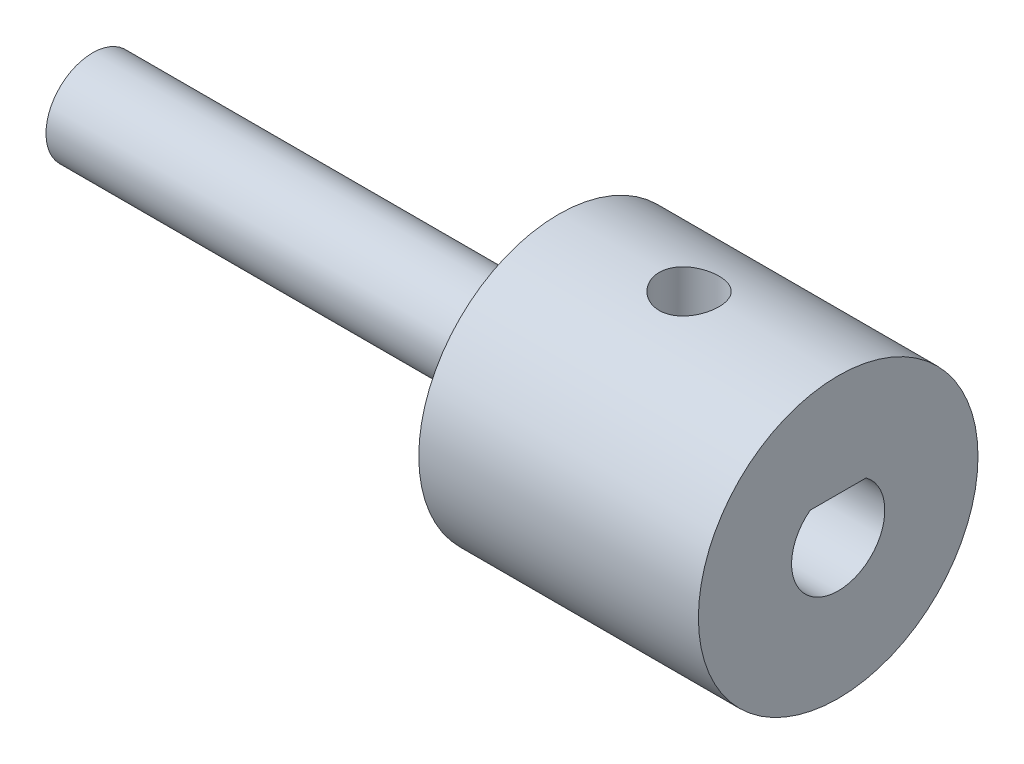
SolidWorks part; units mm, degrees
ref_plane "Front Plane" through (0, 0, 0) normal (0, 0, 1) x (1, 0, 0)
ref_plane "Top Plane" through (0, 0, 0) normal (0, 1, 0) x (1, 0, 0)
ref_plane "Right Plane" through (0, 0, 0) normal (1, 0, 0) x (0, 0, -1)
sketch "Sketch2" plane through (0, 0, 0) normal (0, 0, 1) x (1, 0, 0)
  line L0 (15, 0) -> (15, 7.5)
  line L1 (22, 0) -> (-22, 0) construction
  line L2 (15, 7.5) -> (0, 7.5)
  line L3 (0, 7.5) -> (0, 2.5)
  line L4 (0, 2.5) -> (-25, 2.5)
  line L5 (-25, 2.5) -> (-25, 0)
  line L6 (0, -4.125) -> (0, 4.125) construction
  line L7 (15, 0) -> (-25, 0) construction
  line L8 (15, 0) -> (-25, 0)
  point P10 (0, 5)
  point P11 (-25, 1.25)
  dimension "D1" = 7.5
  dimension "D2" = 2.5
  dimension "D3" = 15
  dimension "D4" = 40
revolve "Revolve1" add sketch "Sketch2" angle 360 about L7
sketch "Sketch3" plane through (15, 0, 0) normal (1, 0, 0) x (0, 0, -1)
  line L0 (-1.5, 2) -> (1.5, 2)
  line L1 (8.25, 0) -> (-8.25, 0) construction
  arc A0 (-1.5, 2) -> (1.5, 2) centre (0, 0) ccw
  dimension "D1" = 5
  dimension "D2" = 2
extrude "Cut-Extrude1" cut sketch "Sketch3" against normal blind 10
sketch "Sketch5" plane through (0, 0, 0) normal (0, 1, 0) x (1, 0, 0)
  line L0 (-8.25, 0) -> (8.25, 0) construction
  line L1 (15, -7.5) -> (15, 7.5) construction
  circle A0 centre (7, 0) radius 1.6
  dimension "D1" = 8
  dimension "D2" = 3.2
extrude "Cut-Extrude2" cut sketch "Sketch5" along normal blind 11
